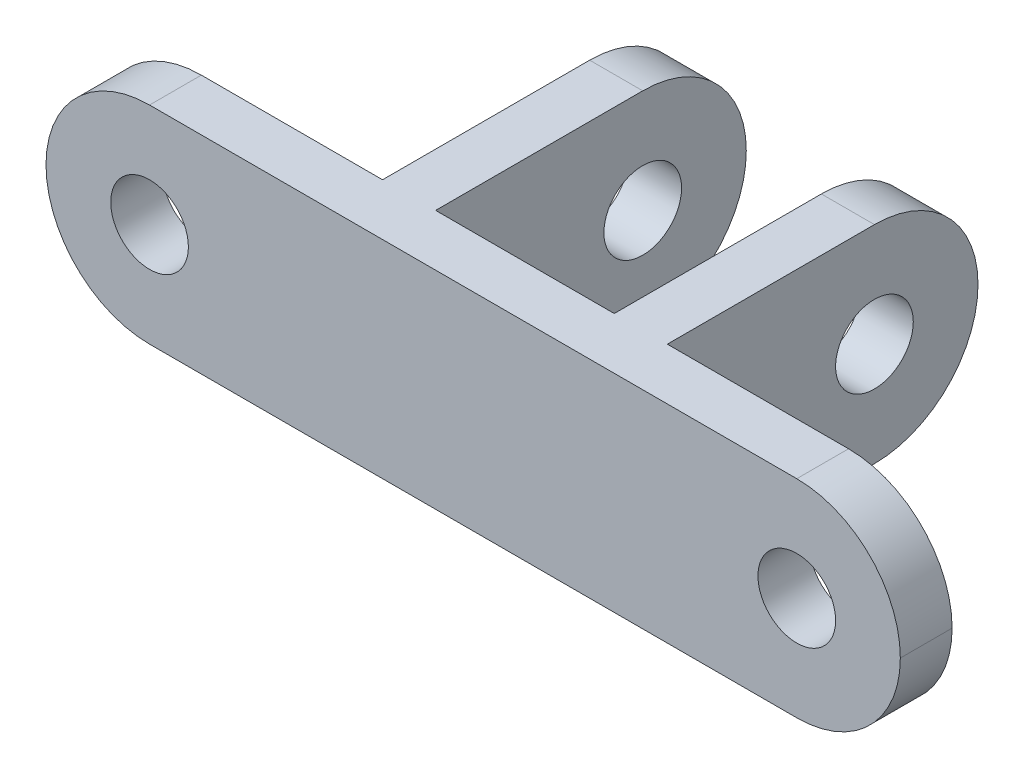
SolidWorks part; units mm, degrees
ref_plane "前视基准面" through (0, 0, 0) normal (0, 0, 1) x (1, 0, 0)
ref_plane "上视基准面" through (0, 0, 0) normal (0, 1, 0) x (1, 0, 0)
ref_plane "右视基准面" through (0, 0, 0) normal (1, 0, 0) x (0, 0, -1)
sketch "草图1" plane through (0, 0, 0) normal (0, 1, 0) x (1, 0, 0)
  line L1 (-16.5, 7) -> (16.5, 7)
  line L2 (-16.5, 7) -> (-16.5, -7)
  line L3 (-16.5, -7) -> (16.5, -7)
  line L4 (16.5, 7) -> (16.5, -7)
  line L5 (-16.5, 7) -> (16.5, -7) construction
  line L6 (-16.5, -7) -> (16.5, 7) construction
  point P0 (0, 0)
  dimension "D1" = 33
  dimension "D2" = 14
extrude "凸台-拉伸1" add sketch "草图1" along normal blind 8
sketch "草图2" plane through (0, 8, 0) normal (0, 1, 0) x (1, 0, 0)
  line L0 (-16.5, -7) -> (16.5, -7) construction
  line L1 (-16.5, 7) -> (-5.5, 7)
  line L2 (-16.5, 7) -> (-16.5, -5)
  line L3 (-16.5, -5) -> (-5.5, -5)
  line L4 (-5.5, 7) -> (-5.5, -5)
  line L5 (16.5, 7) -> (-16.5, 7) construction
  line L6 (16.5, 7) -> (5.5, 7)
  line L7 (16.5, 7) -> (16.5, -5)
  line L8 (16.5, -5) -> (5.5, -5)
  line L9 (5.5, 7) -> (5.5, -5)
  line L10 (3.45, 7) -> (-3.45, 7)
  line L11 (3.45, 7) -> (3.45, -5)
  line L12 (3.45, -5) -> (-3.45, -5)
  line L13 (-3.45, 7) -> (-3.45, -5)
  dimension "D1" = 11
  dimension "D2" = 2
  dimension "D3" = 11
  dimension "D4" = 2
  dimension "D5" = 6.9
  dimension "D6" = 2.05
  dimension "D7" = 2.05
  dimension "D8" = 2
extrude "切除-拉伸1" cut sketch "草图2" against normal through all
fillet "圆角1" radius 4 4 edges at (16.5, 0, 6) (16.5, 8, 6) (-16.5, 0, 6) (-16.5, 8, 6)
fillet "圆角2" radius 4 4 edges at (-4.475, 8, -7) (-4.475, 0, -7) (4.475, 0, -7) (4.475, 8, -7)
sketch "草图3" plane through (5.5, 0, 0) normal (1, 0, 0) x (0, 0, -1)
  circle A0 centre (3, 4) radius 1.5
  dimension "D1" = 3
extrude "切除-拉伸2" cut sketch "草图3" against normal blind 11
sketch "草图4" plane through (0, 0, 7) normal (0, 0, 1) x (1, 0, 0)
  line L0 (12.5, 8) -> (12.5, -1.4547) construction
  circle A0 centre (12.5, 4) radius 1.5
  circle A1 centre (-12.5, 4) radius 1.5
  dimension "D1" = 3
extrude "切除-拉伸3" cut sketch "草图4" against normal through all
